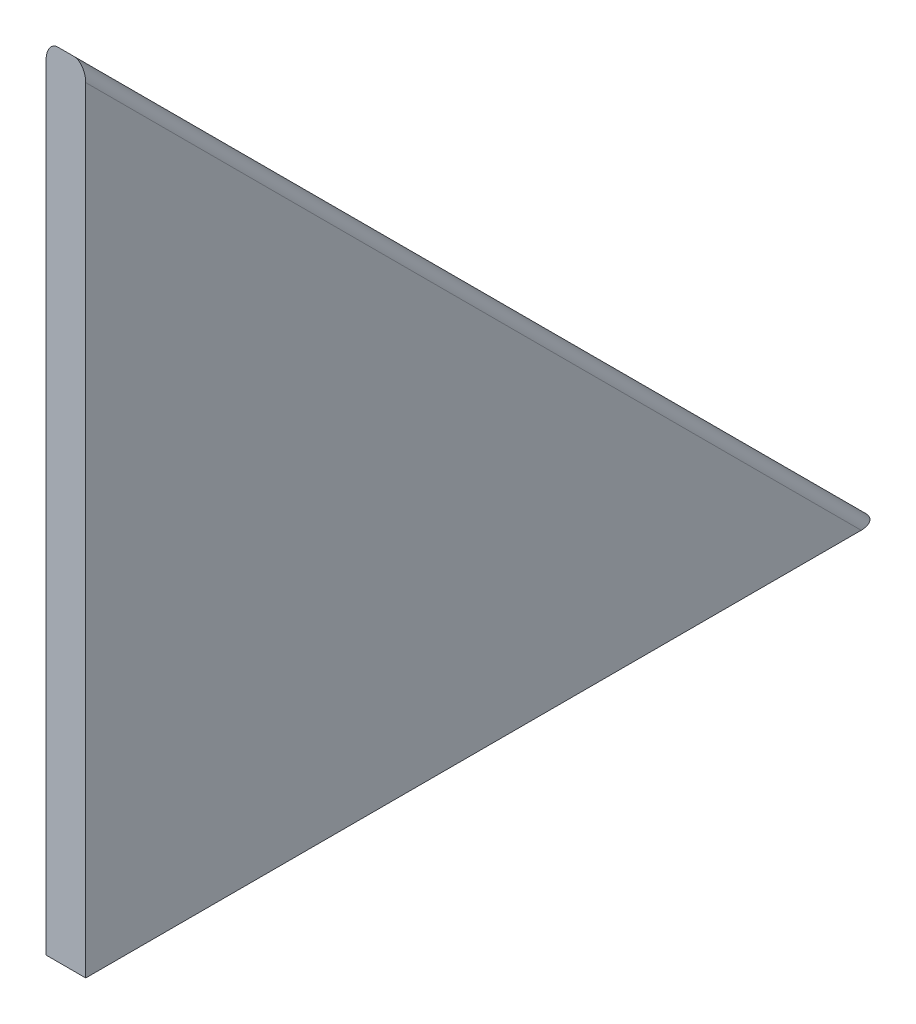
SolidWorks part; units mm, degrees
material "1.0037 (S235JR)"
ref_plane "Front Plane" through (0, 0, 0) normal (0, 0, 1) x (1, 0, 0)
ref_plane "Top Plane" through (0, 0, 0) normal (0, 1, 0) x (1, 0, 0)
ref_plane "Right Plane" through (0, 0, 0) normal (1, 0, 0) x (0, 0, -1)
sketch "Sketch1" plane through (0, 0, 0) normal (1, 0, 0) x (0, 0, -1)
  line L1 (0, 0) -> (200, -200)
  line L3 (200, -200) -> (0, -200)
  line L4 (0, -200) -> (0, 0)
  dimension "D1" = 200
  dimension "D2" = 200
base flange "Base-Flange1" sketch "Sketch1" thickness 10 reverse thickness direction no parameters "D1"=0.7366
fillet "Fillet1" radius 3 2 edges at (-10, -100, -100) (0, -100, -100)
sketch "Bend-Lines1" [suppressed] plane through (0, 0, 0) normal (0, 1, 0) x (1, 0, 0)
sketch "Bounding-Box1" [suppressed] plane through (0, 0, 0) normal (0, 1, 0) x (1, 0, 0)
sheet metal parameters "Sheet-Metal1" thickness 10 parameters "D1"=0.7366
flat pattern "Flat-Pattern1" [suppressed]
sketch "Bend-Lines2" plane through (0, 0, 0) normal (0, 1, 0) x (1, 0, 0)
sketch3d "Bounding-Box2" [suppressed]
  line L0 (0, -200, 0) -> (200, -200, 0) construction
  line L1 (0, 0, 0) -> (200, 0, 0) construction
  line L2 (0, -200, 0) -> (0, 0, 0) construction
  line L3 (200, -200, 0) -> (200, 0, 0) construction
